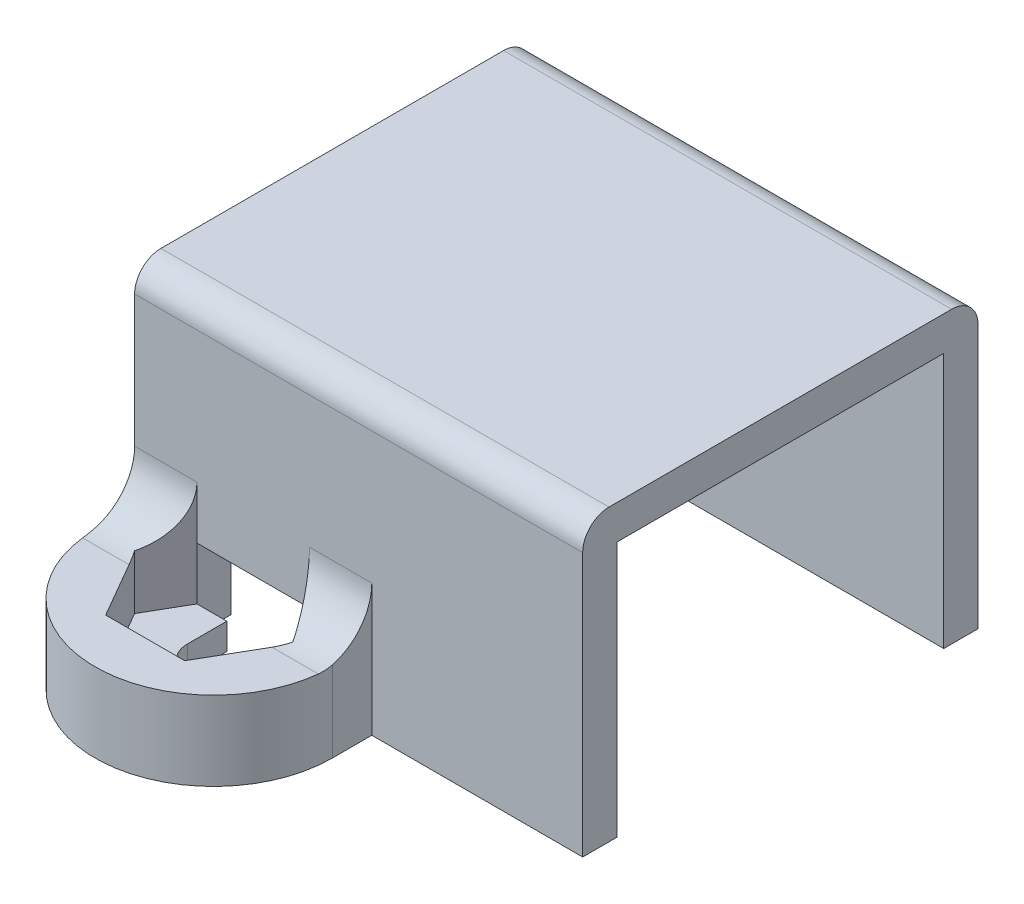
SolidWorks part; units mm, degrees
material "ABS"
ref_plane "Alzado" through (0, 0, 0) normal (0, 0, 1) x (1, 0, 0)
ref_plane "Planta" through (0, 0, 0) normal (0, 1, 0) x (1, 0, 0)
ref_plane "Vista lateral" through (0, 0, 0) normal (1, 0, 0) x (0, 0, -1)
sketch "Croquis1" plane through (0, 0, 0) normal (0, 1, 0) x (1, 0, 0)
  line L1 (-8.5, -13.5) -> (8.5, -13.5)
  line L2 (-8.5, -13.5) -> (-8.5, 13.5)
  line L3 (-8.5, 13.5) -> (8.5, 13.5)
  line L4 (8.5, -13.5) -> (8.5, 13.5)
  line L5 (-8.5, -13.5) -> (8.5, 13.5) construction
  line L6 (-8.5, 13.5) -> (8.5, -13.5) construction
  point P0 (0, 0)
  dimension "D1" = 17
  dimension "D2" = 27
extrude "Saliente-Extruir1" add sketch "Croquis1" along normal blind 11
sketch "Croquis2" plane through (0, 11, 0) normal (0, 1, 0) x (1, 0, 0)
  line L1 (-8.5, -7.5) -> (8.5, -7.5) construction
  line L2 (-8.5, 13.5) -> (-8.5, -13.5) construction
  line L3 (-8.5, 7.5) -> (8.5, 7.5) construction
  line L4 (-8.5, 13.5) -> (8.5, 13.5)
  line L5 (-8.5, 13.5) -> (-8.5, 7.5)
  line L6 (-8.5, 7.5) -> (8.5, 7.5)
  line L7 (8.5, 13.5) -> (8.5, 7.5)
  line L8 (-8.5, -7.5) -> (8.5, -7.5)
  line L9 (-8.5, -7.5) -> (-8.5, -13.5)
  line L10 (-8.5, -13.5) -> (8.5, -13.5)
  line L11 (8.5, -7.5) -> (8.5, -13.5)
  point P0 (0, 0)
  dimension "D1" = 6
  dimension "D2" = 6
extrude "Cortar-Extruir1" cut sketch "Croquis2" against normal blind 6
sketch "Croquis3" plane through (0, 0, 13.5) normal (0, 0, 1) x (1, 0, 0)
  line L0 (8.5, 5) -> (-8.5, 5) construction
  line L1 (8.5, 0) -> (0.5, 0)
  line L2 (8.5, 0) -> (8.5, 5)
  line L3 (8.5, 5) -> (0.5, 5)
  line L4 (0.5, 0) -> (0.5, 5)
  dimension "D1" = 8
extrude "Cortar-Extruir2" cut sketch "Croquis3" against normal blind 6
sketch "Croquis4" plane through (0, 0, -13.5) normal (0, 0, -1) x (-1, 0, 0)
  line L0 (8.5, 5) -> (-8.5, 5) construction
  line L1 (-8.5, 0) -> (-0.5, 0)
  line L2 (-8.5, 0) -> (-8.5, 5)
  line L3 (-8.5, 5) -> (-0.5, 5)
  line L4 (-0.5, 0) -> (-0.5, 5)
  dimension "D1" = 8
extrude "Cortar-Extruir3" cut sketch "Croquis4" against normal blind 6
sketch "Croquis5" plane through (0, 5, 0) normal (0, 1, 0) x (1, 0, 0)
  line L0 (-8.5, 9) -> (-8.5, 13.5)
  line L1 (0.5, 13.5) -> (-8.5, 13.5) construction
  line L2 (0.5, 7.5) -> (0.5, 13.5) construction
  line L3 (-8.5, 13.5) -> (-8.5, 7.5) construction
  line L4 (-8.5, 13.5) -> (0.5, 13.5)
  line L5 (0.5, 13.5) -> (0.5, 9)
  line L6 (-8.5, -9) -> (-8.5, -13.5)
  line L14 (-8.5, -13.5) -> (0.5, -13.5) construction
  line L15 (-8.5, -7.5) -> (-8.5, -13.5) construction
  line L16 (0.5, -7.5) -> (0.5, -13.5) construction
  line L17 (-8.5, -13.5) -> (0.5, -13.5)
  line L18 (0.5, -13.5) -> (0.5, -9)
  line L19 (0.5, -7.5) -> (-8.5, -7.5) construction
  arc A0 (-4, 13.5) -> (0.5, 9) centre (-4, 9) cw
  arc A1 (-8.5, 9) -> (-4, 13.5) centre (-4, 9) cw
  arc A2 (-4, -13.5) -> (-8.5, -9) centre (-4, -9) cw
  arc A3 (-4, -13.5) -> (0.5, -9) centre (-4, -9) ccw
  line M1 (0.5, 7.5) -> (0.5, 13.5)
  line M2 (0.5, 13.5) -> (-8.5, 13.5)
  line M3 (-8.5, 13.5) -> (-8.5, 7.5)
  dimension "D1" = 4.5
  dimension "D2" = 1.5
extrude "Cortar-Extruir8" cut sketch "Croquis5" against normal blind 6 contours A1 L4 M3 | A0 M2 M1 | L17 A2 L6 | A3 L17 L18 region at (-0.5052, 5, -12.4948) region at (-7.4948, 5, -12.4948) region at (-7.4948, 5, 12.4948) region at (-0.5052, 5, 12.4948)
sketch "Croquis7" plane through (0, 5, 0) normal (0, 1, 0) x (1, 0, 0)
  line L0 (-8.5, 7.5) -> (-8.5, 9)
  line L1 (-8.5, 7.5) -> (0.5, 7.5)
  line L2 (-8.5, 7.5) -> (8.5, 7.5) construction
  line L3 (-8.5, 7.5) -> (0.5, 7.5) construction
  line L4 (0.5, 7.5) -> (0.5, 9)
  line L5 (-8.5, -9) -> (-8.5, -7.5)
  line L7 (-8.5, -7.5) -> (0.5, -7.5)
  line L8 (0.5, -7.5) -> (0.5, -9)
  arc A0 (0.5, 9) -> (-8.5, 9) centre (-4, 9) ccw
  arc A1 (-8.5, -9) -> (0.5, -9) centre (-4, -9) ccw
  arc A2 (-8.5, -9) -> (0.5, -9) centre (-4, -9) ccw construction
  dimension "D1" = 4.5
extrude "Cortar-Extruir16" cut sketch "Croquis7" against normal blind 2
sketch "Croquis10" plane through (0, 3, 0) normal (0, 1, 0) x (1, 0, 0)
  line L0 (-6.134, 7.5) -> (-1.866, 7.5)
  line L1 (-8.5, 7.5) -> (0.5, 7.5) construction
  line L3 (-1, 9) -> (-2.5, 11.5981)
  line L4 (-2.5, 11.5981) -> (-5.5, 11.5981)
  line L5 (-5.5, 11.5981) -> (-7, 9)
  line L6 (-7, 9) -> (-6.134, 7.5)
  line L8 (-1.866, 7.5) -> (-1, 9)
  line L9 (-4, 6.4019) -> (-2.5, 6.4019) [skipped]
  arc A1 (-1.8787, 7.5) -> (-1.75, 7.701) centre (-4, 9) ccw construction
  arc A2 (-6.25, 7.701) -> (-6.1213, 7.5) centre (-4, 9) ccw construction
  dimension "D1" = 3
  dimension "D2" = 1.5
extrude "Cortar-Extruir17" cut sketch "Croquis10" against normal blind 2
sketch "Croquis11" plane through (0, 3, 0) normal (0, 1, 0) x (1, 0, 0)
  line L1 (0.5, -7.5) -> (-8.5, -7.5) construction
  line L2 (-6.134, -7.5) -> (-1.866, -7.5)
  line L3 (-1, -9) -> (-1.866, -7.5)
  line L5 (-6.134, -7.5) -> (-7, -9)
  line L6 (-7, -9) -> (-5.5, -11.5981)
  line L7 (-5.5, -11.5981) -> (-2.5, -11.5981)
  line L8 (-2.5, -11.5981) -> (-1, -9)
  line L9 (8.5, -7.5) -> (-8.5, -7.5) construction
  line L11 (-2.5, -6.4019) -> (-4, -6.4019) [skipped]
  arc A0 (-1.75, -7.701) -> (-1.8787, -7.5) centre (-4, -9) ccw construction
  arc A1 (-6.1213, -7.5) -> (-6.25, -7.701) centre (-4, -9) ccw construction
extrude "Cortar-Extruir18" cut sketch "Croquis11" against normal blind 2
fillet "Redondeo5" radius 2 4 edges at (-0.683, 3, 7.5) (-7.317, 3, 7.5) (-0.683, 3, -7.5) (-7.317, 3, -7.5)
sketch "Croquis12" plane through (-8.5, 0, 0) normal (-1, 0, 0) x (0, 0, 1)
  line L0 (-6.2, 0) -> (6.2, 0)
  line L1 (-9, 0) -> (9, 0) construction
  line L5 (-6.2, 0) -> (-6.2, 7.7)
  line L7 (6.2, 0) -> (6.2, 7.7)
  line L10 (-4.2, 9.7) -> (4.2, 9.7)
  arc A0 (-4.2, 9.7) -> (-6.2, 7.7) centre (-4.2, 7.7) ccw
  arc A1 (6.2, 7.7) -> (4.2, 9.7) centre (4.2, 7.7) ccw
  dimension "D1" = 2
  dimension "D2" = 8.4
extrude "Cortar-Extruir19" cut sketch "Croquis12" against normal blind 17
sketch "Croquis13" plane through (8.5, 0, 0) normal (1, 0, 0) x (0, 0, -1)
  line L0 (-6.2, 7.7) -> (-6.2, 9.7)
  line L1 (-6.2, 9.7) -> (-4.2, 9.7)
  line L2 (6.2, 7.7) -> (6.2, 9.7)
  line L3 (6.2, 9.7) -> (4.2, 9.7)
  arc A0 (-4.2, 9.7) -> (-6.2, 7.7) centre (-4.2, 7.7) ccw
  arc A1 (6.2, 7.7) -> (4.2, 9.7) centre (4.2, 7.7) ccw construction
  arc A2 (6.2, 7.7) -> (4.2, 9.7) centre (4.2, 7.7) ccw
extrude "Cortar-Extruir20" cut sketch "Croquis13" against normal blind 10
fillet "Redondeo6" radius 1 2 edges at (0, 11, -7.5) (0, 11, 7.5)
sketch "Croquis14" plane through (0, 1, 0) normal (0, 1, 0) x (1, 0, 0)
  line L0 (-5, 9) -> (-5, 7.5)
  line L1 (-8.5, 7.5) -> (8.5, 7.5) construction
  line L2 (-3, 9) -> (-3, 7.5)
  line L3 (-6.134, 7.5) -> (-1.866, 7.5) construction
  line L4 (-3, 7.5) -> (-5, 7.5)
  arc A1 (-3, 9) -> (-5, 9) centre (-4, 9) ccw
extrude "Cortar-Extruir21" cut sketch "Croquis14" against normal blind 1 contours A1 L0 L4 L2
sketch "Croquis15" plane through (0, 1, 0) normal (0, 1, 0) x (1, 0, 0)
  line L0 (-5, -9) -> (-5, -7.5)
  line L1 (-1.866, -7.5) -> (-6.134, -7.5) construction
  line L2 (-5, -7.5) -> (-3, -7.5)
  line L3 (-3, -7.5) -> (-3, -9)
  arc A1 (-5, -9) -> (-3, -9) centre (-4, -9) ccw
extrude "Cortar-Extruir22" cut sketch "Croquis15" against normal blind 1
sketch "Croquis16" plane through (0, 0, -7.5) normal (0, 0, -1) x (-1, 0, 0)
  line L0 (1.866, 3) -> (6.134, 3)
  line L1 (1.866, 1) -> (1.866, 5) construction
  line L2 (6.134, 1) -> (6.134, 5) construction
  line L3 (6.134, 3) -> (6.134, 1)
  line L4 (6.134, 1) -> (5, 1)
  line L7 (3, 1) -> (1.866, 1)
  line L8 (1.866, 1) -> (1.866, 3)
  line L9 (3, 1) -> (5, 1)
extrude "Cortar-Extruir26" cut sketch "Croquis16" against normal blind 1.3 contours L0 L3 L4 L9 L7 L8
sketch "Croquis17" plane through (0, 0, 7.5) normal (0, 0, 1) x (1, 0, 0)
  line L0 (-6.134, 3) -> (-1.866, 3)
  line L1 (-6.134, 1) -> (-6.134, 5) construction
  line L2 (-1.866, 1) -> (-1.866, 5) construction
  line L3 (-1.866, 3) -> (-1.866, 1)
  line L4 (-1.866, 1) -> (-6.134, 1)
  line L5 (-6.134, 1) -> (-6.134, 3)
extrude "Cortar-Extruir27" cut sketch "Croquis17" against normal blind 1.3
sketch "Croquis19" plane through (0, 0, 6.2) normal (0, 0, -1) x (-1, 0, 0)
  line L0 (1.866, 1) -> (1.866, 0)
  line L1 (-8.5, 0) -> (8.5, 0) construction
  line L2 (1.866, 0) -> (6.134, 0)
  line L3 (6.134, 0) -> (6.134, 1)
  line L4 (6.134, 1) -> (1.866, 1)
extrude "Cortar-Extruir28" cut sketch "Croquis19" against normal blind 1.3
sketch "Croquis20" plane through (0, 0, -6.2) normal (0, 0, 1) x (1, 0, 0)
  line L0 (-6.134, 1) -> (-1.866, 1)
  line L1 (-1.866, 1) -> (-1.866, 0)
  line L2 (8.5, 0) -> (-8.5, 0) construction
  line L3 (-1.866, 0) -> (-6.134, 0)
  line L4 (-6.134, 0) -> (-6.134, 1)
extrude "Cortar-Extruir29" cut sketch "Croquis20" against normal blind 1.3
